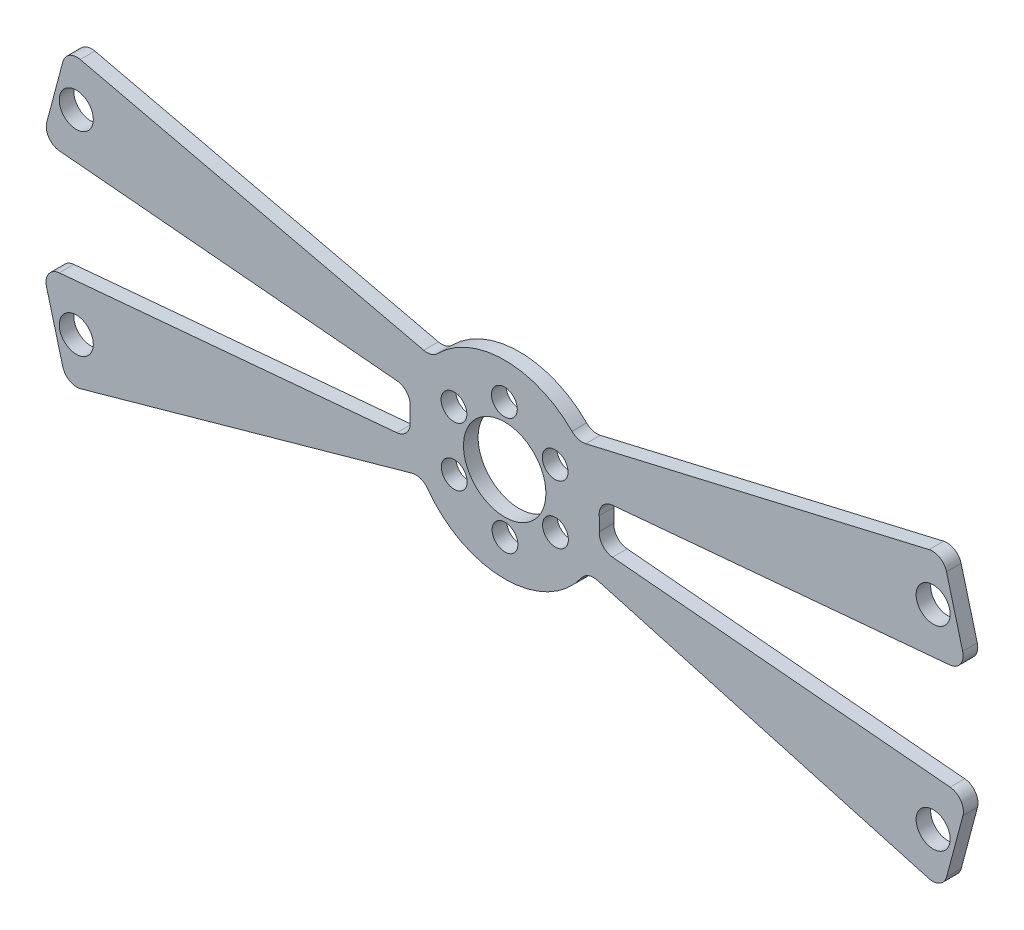
SolidWorks part; units mm, degrees
ref_plane "前视基准面" through (0, 0, 0) normal (0, 0, 1) x (1, 0, 0)
ref_plane "上视基准面" through (0, 0, 0) normal (0, 1, 0) x (1, 0, 0)
ref_plane "右视基准面" through (0, 0, 0) normal (1, 0, 0) x (0, 0, -1)
other "Configuration Table"
sketch "草图1" plane through (0, 0, 0) normal (0, 0, 1) x (1, 0, 0)
  line L24 (-44.2718, 12.9002) -> (-114.8041, 29.3396)
  line L25 (-118.3844, 27.1883) -> (-121.7019, 14.703)
  line L26 (-119.0708, 10.9447) -> (-49.7708, 4.7219)
  line L27 (-49.7848, -4.5305) -> (-119.1208, -10.7565)
  line L28 (-121.7519, -14.5148) -> (-118.4176, -27.0637)
  line L29 (-114.7111, -29.1827) -> (-46.7133, -10.1908)
  line L30 (-8.5614, -10.1908) -> (59.4364, -29.1827)
  line L31 (63.1428, -27.0637) -> (66.4772, -14.5148)
  line L32 (63.8461, -10.7565) -> (-5.4899, -4.5305)
  line L33 (-5.5039, 4.7219) -> (63.7961, 10.9447)
  line L34 (66.4271, 14.703) -> (63.1097, 27.1883)
  line L35 (59.5293, 29.3396) -> (-11.0029, 12.9002)
  arc A40 (-114.8041, 29.3396) -> (-118.3844, 27.1883) centre (-115.485, 26.4179) ccw
  arc A41 (-121.7019, 14.703) -> (-119.0708, 10.9447) centre (-118.8025, 13.9326) ccw
  arc A42 (-47.0481, 1.5024) -> (-49.7708, 4.7219) centre (-50.0391, 1.7339) ccw
  arc A43 (-47.0481, 1.5024) -> (-47.0602, -1.3365) centre (-27.6374, 0) ccw
  arc A44 (-49.7848, -4.5305) -> (-47.0602, -1.3365) centre (-50.0531, -1.5425) ccw
  arc A45 (-119.1208, -10.7565) -> (-121.7519, -14.5148) centre (-118.8525, -13.7444) ccw
  arc A46 (-118.4176, -27.0637) -> (-114.7111, -29.1827) centre (-115.5182, -26.2933) ccw
  arc A47 (-43.467, -11.3337) -> (-46.7133, -10.1908) centre (-45.9063, -13.0802) ccw
  arc A48 (-43.467, -11.3337) -> (-11.8077, -11.3337) centre (-27.6374, 0) ccw
  arc A49 (-8.5614, -10.1908) -> (-11.8077, -11.3337) centre (-9.3684, -13.0802) ccw
  arc A50 (59.4364, -29.1827) -> (63.1428, -27.0637) centre (60.2434, -26.2933) ccw
  arc A51 (66.4772, -14.5148) -> (63.8461, -10.7565) centre (63.5778, -13.7444) ccw
  arc A52 (-8.2145, -1.3365) -> (-5.4899, -4.5305) centre (-5.2216, -1.5425) ccw
  arc A53 (-8.2145, -1.3365) -> (-8.2267, 1.5024) centre (-27.6374, 0) ccw
  arc A54 (-5.5039, 4.7219) -> (-8.2267, 1.5024) centre (-5.2356, 1.7339) ccw
  arc A55 (63.7961, 10.9447) -> (66.4271, 14.703) centre (63.5277, 13.9326) ccw
  arc A56 (63.1097, 27.1883) -> (59.5293, 29.3396) centre (60.2103, 26.4179) ccw
  arc A57 (-13.8139, 13.7093) -> (-11.0029, 12.9002) centre (-11.6839, 15.8218) ccw
  arc A58 (-13.8139, 13.7093) -> (-41.4608, 13.7093) centre (-27.6374, 0) ccw
  arc A59 (-44.2718, 12.9002) -> (-41.4608, 13.7093) centre (-43.5909, 15.8218) ccw
  dimension "D1" = 3
  dimension "D2" = 19.4688
  dimension "D3" = 59.4364
  dimension "D4" = 59.5293
  dimension "D5" = 60.2103
  dimension "D6" = 60.2434
  dimension "D7" = 63.1097
  dimension "D8" = 63.5277
  dimension "D9" = 63.5778
  dimension "D10" = 63.7961
  dimension "D11" = 5.2216
  dimension "D12" = 5.2356
  dimension "D13" = 8.2145
extrude "凸台-拉伸2" add sketch "草图1" along normal blind 3 contours A59 L24 A40 L25 A41 L26 A42 A43 A44 L27 A45 L28 A46 L29 A47 A48 A49 L30 A50 L31 A51 L32 A52 A53 A54 L33 A55 L34 A56 L35 A57 A58 region at (-27.6374, 0.8009, 0)
sketch "草图4" plane through (0, 0, 3) normal (0, 0, 1) x (1, 0, 0)
  circle A2 centre (-115.6374, -20) radius 3.5
  circle A3 centre (-115.6374, 20) radius 3.5
  circle A19 centre (60.3626, -20) radius 3.5
  circle A20 centre (60.3626, 20) radius 3.5
  arc A21 (-37.9849, -8.7035) -> (-38.0122, -3.4036) centre (-37.9986, -6.0535) ccw
  arc A22 (-38.0122, -3.4036) -> (-37.9849, -8.7035) centre (-37.9986, -6.0535) ccw
  arc A23 (-25.2737, -13.313) -> (-29.8772, -10.6867) centre (-27.5755, -11.9998) ccw
  arc A24 (-29.8772, -10.6867) -> (-25.2737, -13.313) centre (-27.5755, -11.9998) ccw
  arc A25 (-19.5023, -7.2831) -> (-14.9261, -4.6095) centre (-17.2142, -5.9463) ccw
  arc A26 (-14.9261, -4.6095) -> (-19.5023, -7.2831) centre (-17.2142, -5.9463) ccw
  circle A27 centre (-27.6374, 0) radius 8.4629
  arc A28 (-17.2625, 3.4036) -> (-17.2898, 8.7035) centre (-17.2761, 6.0535) ccw
  arc A29 (-17.2898, 8.7035) -> (-17.2625, 3.4036) centre (-17.2761, 6.0535) ccw
  arc A30 (-25.3975, 10.6867) -> (-30.001, 13.313) centre (-27.6992, 11.9998) ccw
  arc A31 (-30.001, 13.313) -> (-25.3975, 10.6867) centre (-27.6992, 11.9998) ccw
  arc A32 (-35.7724, 7.2831) -> (-40.3486, 4.6095) centre (-38.0605, 5.9463) ccw
  arc A33 (-40.3486, 4.6095) -> (-35.7724, 7.2831) centre (-38.0605, 5.9463) ccw
extrude "切除-拉伸1" cut sketch "草图4" against normal blind 3
